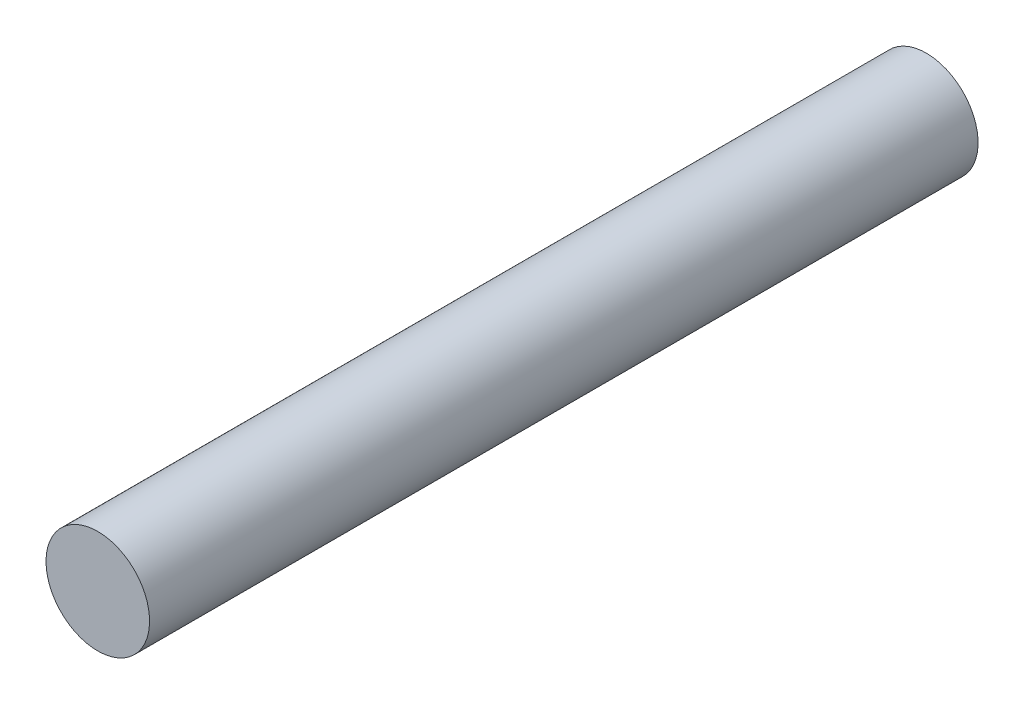
SolidWorks part; units mm, degrees
ref_plane "Front" through (0, 0, 0) normal (0, 0, 1) x (1, 0, 0)
ref_plane "Top" through (0, 0, 0) normal (0, 1, 0) x (1, 0, 0)
ref_plane "Right" through (0, 0, 0) normal (1, 0, 0) x (0, 0, -1)
sketch "Sketch1" plane through (0, 0, 0) normal (0, 0, 1) x (1, 0, 0)
  circle A0 centre (0, 4.3656) radius 2.3813
  dimension "D1" = 4.7625
extrude "Boss-Extrude1" add sketch "Sketch1" along normal blind 38.1
ref_axis "Axis1" through (0, 4.3656, 38.1) along (0, 0, -1)
